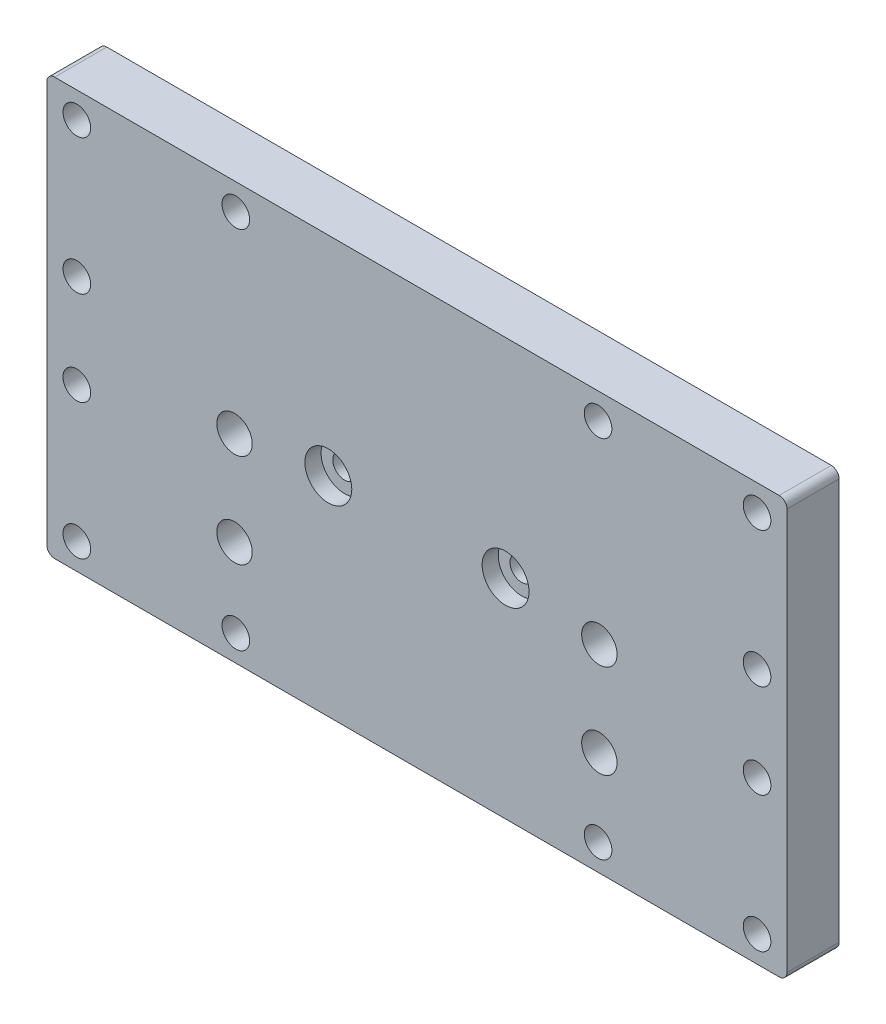
SolidWorks part; units mm, degrees
ref_plane "Front Plane" through (0, 0, 0) normal (0, 0, 1) x (1, 0, 0)
ref_plane "Top Plane" through (0, 0, 0) normal (0, 1, 0) x (1, 0, 0)
ref_plane "Right Plane" through (0, 0, 0) normal (1, 0, 0) x (0, 0, -1)
sketch "Sketch1" plane through (0, 0, 0) normal (0, 0, 1) x (1, 0, 0)
  line L1 (-71, -40) -> (71, -40)
  line L2 (-71, -40) -> (-71, 40)
  line L3 (-71, 40) -> (71, 40)
  line L4 (71, -40) -> (71, 40)
  line L5 (-71, -40) -> (71, 40) construction
  line L6 (-71, 40) -> (71, -40) construction
  point P0 (0, 0)
  dimension "D1" = 80
  dimension "D2" = 142
extrude "Boss-Extrude1" add sketch "Sketch1" along normal mid plane 10
hole_wizard "M5 Clearance Hole1" positions "Sketch6" profile "Sketch5" hole size "M5" standard "ANSI Metric" end condition through all
sketch "Sketch6" plane through (0, 0, 5) normal (0, 0, 1) x (1, 0, 0)
  line L1 (-65.25, 35) -> (-34.75, 35) construction
  line L2 (-65.25, 35) -> (-65.25, 9) construction
  line L3 (-65.25, 9) -> (-34.75, 9) construction
  line L4 (-34.75, 35) -> (-34.75, 9) construction
  line L5 (-65.25, 35) -> (-34.75, 9) construction
  line L6 (-65.25, 9) -> (-34.75, 35) construction
  line L7 (-71, 40) -> (-71, -40) construction
  line L8 (71, 40) -> (-71, 40) construction
  point P0 (-65.25, 35)
  point P2 (-34.75, 35)
  point P4 (-65.25, 9)
  dimension "D1" = 5.75
  dimension "D2" = 5
  dimension "D3" = 26
  dimension "D4" = 30.5
sketch "Sketch5" plane through (-65.25, 35, 5) normal (1, 0, 0) x (0, -1, 0)
  line L0 (0, 0) -> (0, 10)
  line L1 (0, 10) -> (2.65, 10)
  line L2 (2.65, 10) -> (2.65, 0)
  line L5 (2.65, 0) -> (0, 0)
  line L11 (0, -6.35) -> (0, 107.95) construction
  dimension "Thru Hole Dia." = 5.3
  dimension "Thru Hole Depth" = 10
mirror "Mirror1" about plane through (0, 0, 0) normal (1, 0, 0) of "M5 Clearance Hole1"
mirror "Mirror2" about plane through (0, 0, 0) normal (0, 1, 0) of "Mirror1"
hole_wizard "CBORE for M4 Pan Head Machine Screw1" positions "Sketch8" profile "Sketch7" counterbore size "M4" standard "ANSI Metric" end condition through all
sketch "Sketch8" plane through (-50.3084, 7.5334, 5) normal (0, 0, 1) x (1, 0, 0)
  line L0 (-1000, -7.5334) -> (49000, -7.5334) construction
  point P0 (33.3084, -7.5334)
  point P2 (67.3084, -7.5334)
  dimension "D1" = 17
  dimension "D2" = 17
sketch "Sketch7" plane through (-17, 0, 5) normal (1, 0, 0) x (0, -1, 0)
  line L0 (0, 0) -> (0, 10)
  line L1 (0, 10) -> (2.25, 10)
  line L3 (2.25, 10) -> (2.25, 3.1)
  line L4 (2.25, 3.1) -> (4.5, 3.1)
  line L5 (4.5, 3.1) -> (4.5, 0)
  line L7 (4.5, 0) -> (0, 0)
  line L11 (0, -6.35) -> (0, 107.95) construction
  dimension "Thru Hole Dia." = 4.5
  dimension "Thru Hole Depth" = 10
  dimension "C'Bore Dia." = 9
  dimension "C'Bore Depth" = 3.1
hole_wizard "M8x1.25 Tapped Hole1" positions "Sketch10" profile "Sketch9" tap size "M8x1.25" standard "ANSI Metric" end condition through all
sketch "Sketch10" plane through (0, 0, 5) normal (0, 0, 1) x (1, 0, 0)
  line L1 (-35, -20) -> (35, -20) construction
  line L2 (-35, -20) -> (-35, -2) construction
  line L3 (-35, -2) -> (35, -2) construction
  line L4 (35, -20) -> (35, -2) construction
  line L5 (-35, -20) -> (35, -2) construction
  line L6 (-35, -2) -> (35, -20) construction
  line L7 (-71, -40) -> (71, -40) construction
  point P0 (-35, -2)
  point P2 (35, -2)
  point P4 (35, -20)
  point P6 (-35, -20)
  dimension "D1" = 70
  dimension "D2" = 35
  dimension "D3" = 20
  dimension "D4" = 18
sketch "Sketch9" plane through (-35, -2, 5) normal (1, 0, 0) x (0, -1, 0)
  line L0 (0, 0) -> (0, 10)
  line L1 (0, 10) -> (3.4, 10)
  line L2 (3.4, 10) -> (3.4, 0)
  line L5 (3.4, 0) -> (0, 0)
  line L11 (0, -6.35) -> (0, 107.95) construction
  dimension "Thru Tap Drill Dia." = 6.8
  dimension "Thru Tap Drill Depth" = 10
cosmetic thread "Hole Thread1" parameters "D2"=8
cosmetic thread "Hole Thread2" parameters "D2"=8
cosmetic thread "Hole Thread3" parameters "D2"=8
cosmetic thread "Hole Thread4" parameters "D2"=8
fillet "Fillet1" radius 1.5 4 edges at (-71, -40, 0) (71, -40, 0) (71, 40, 0) (-71, 40, 0)
